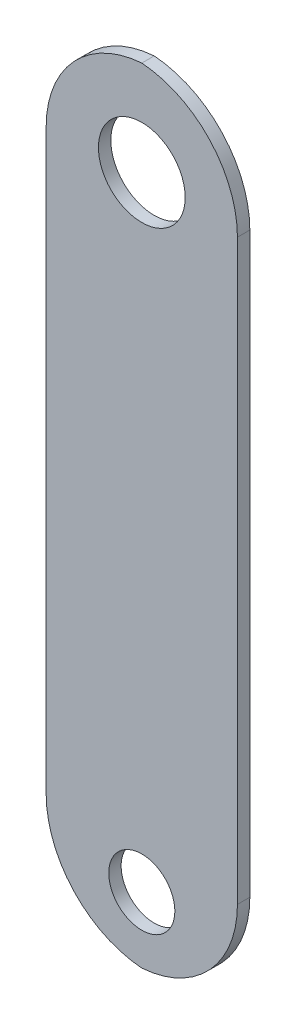
SolidWorks part; units mm, degrees
ref_plane "Front Plane" through (0, 0, 0) normal (0, 0, 1) x (1, 0, 0)
ref_plane "Top Plane" through (0, 0, 0) normal (0, 1, 0) x (1, 0, 0)
ref_plane "Right Plane" through (0, 0, 0) normal (1, 0, 0) x (0, 0, -1)
sketch "Sketch1" plane through (0, 0, 0) normal (0, 0, 1) x (1, 0, 0)
  line L1 (23.15, -94.93) -> (-23.15, -94.93)
  line L2 (23.15, -94.93) -> (23.15, 94.93)
  line L3 (23.15, 94.93) -> (-23.15, 94.93)
  line L4 (-23.15, -94.93) -> (-23.15, 94.93)
  line L5 (23.15, -94.93) -> (-23.15, 94.93) construction
  line L6 (23.15, 94.93) -> (-23.15, -94.93) construction
  circle A0 centre (0, 71.93) radius 10.5
  circle A1 centre (0, -78.93) radius 8
  point P0 (0, 0)
  dimension "D3" = 21
  dimension "D6" = 16
  dimension "D1" = 189.86
  dimension "D2" = 46.3
  dimension "D4" = 23.15
  dimension "D5" = 23
  dimension "D7" = 23.15
  dimension "D8" = 16
extrude "Boss-Extrude1" add sketch "Sketch1" along normal blind 3
fillet "Fillet1" radius 25 4 edges at (23.15, -94.93, 1.5) (-23.15, -94.93, 1.5) (-23.15, 94.93, 1.5) (23.15, 94.93, 1.5)
